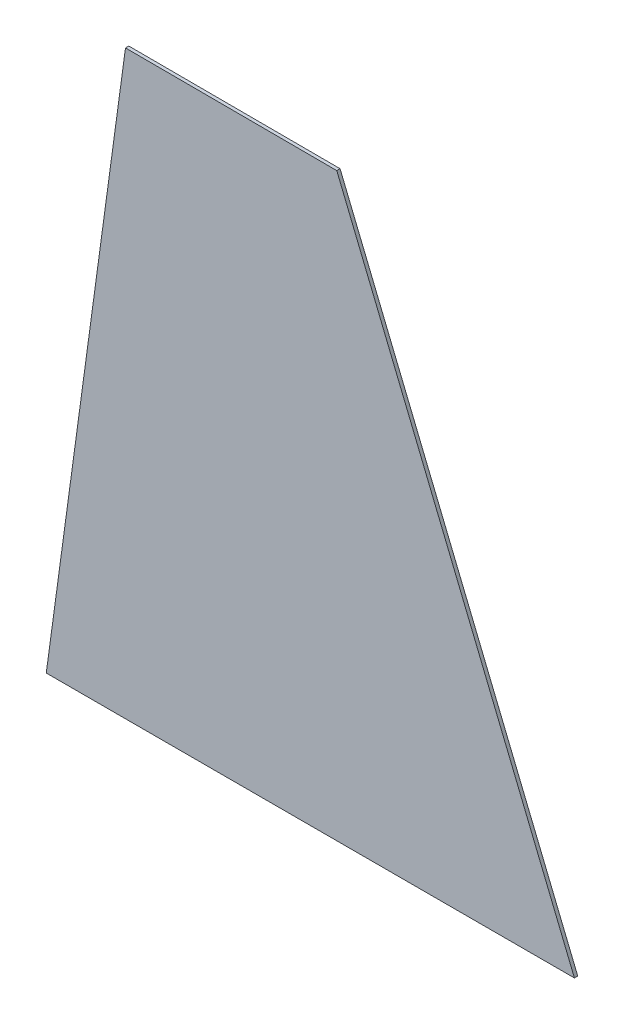
SolidWorks part; units mm, degrees
material "Glass"
ref_plane "Front Plane" through (0, 0, 0) normal (0, 0, 1) x (1, 0, 0)
ref_plane "Top Plane" through (0, 0, 0) normal (0, 1, 0) x (1, 0, 0)
ref_plane "Right Plane" through (0, 0, 0) normal (1, 0, 0) x (0, 0, -1)
sketch "Sketch1" plane through (0, 0, 0) normal (0, 0, 1) x (1, 0, 0)
  line L0 (-76.2, 0) -> (0, 0)
  line L1 (0, 0) -> (177.8, 0)
  line L3 (0, 558.8) -> (203.1992, 558.2225)
  line L5 (-76.2, 0) -> (0, 558.8)
  line L6 (203.1992, 558.2225) -> (431.7992, 0)
  line L7 (177.8, 0) -> (431.7992, 0)
  dimension "D1" = 203.2
  dimension "D2" = 558.8
  dimension "D4" = 76.2
  dimension "D5" = 228.6
extrude "Boss-Extrude1" add sketch "Sketch1" along normal blind 3.175
